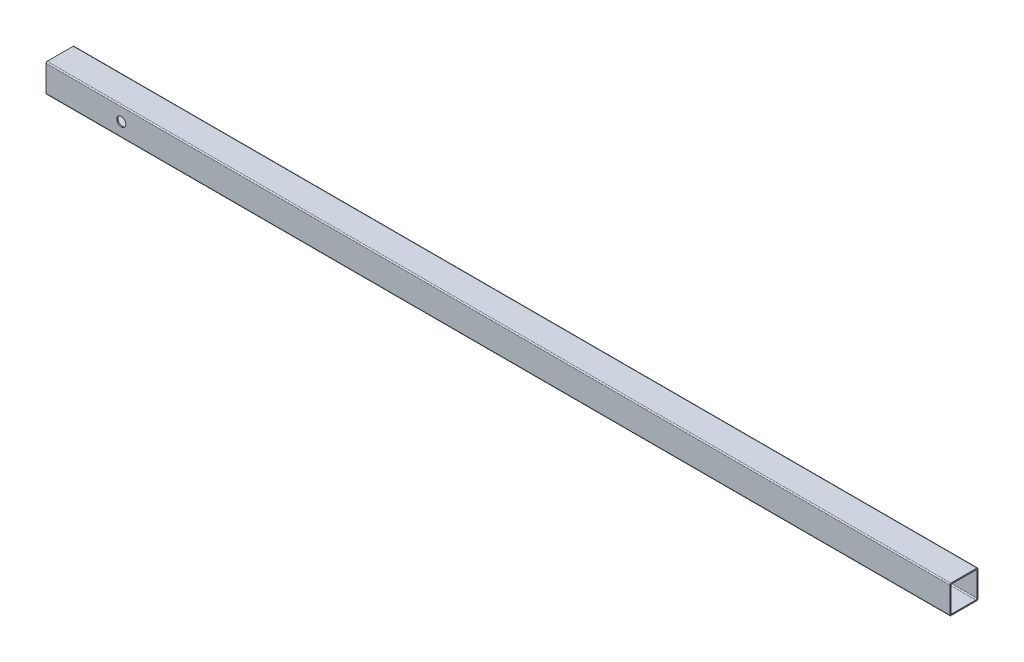
SolidWorks part; units mm, degrees
material "Thornel Mat VMA"
ref_plane "Front Plane" through (0, 0, 0) normal (0, 0, 1) x (1, 0, 0)
ref_plane "Top Plane" through (0, 0, 0) normal (0, 1, 0) x (1, 0, 0)
ref_plane "Right Plane" through (0, 0, 0) normal (1, 0, 0) x (0, 0, -1)
sketch "Sketch2" plane through (0, 0, 0) normal (1, 0, 0) x (0, 0, -1)
  line L1 (0.762, 0) -> (18.288, 0)
  line L2 (0, 0.762) -> (0, 18.288)
  line L3 (0.762, 19.05) -> (18.288, 19.05)
  line L4 (19.05, 0.762) -> (19.05, 18.288)
  line L5 (1.524, 0.762) -> (17.526, 0.762)
  line L6 (0.762, 1.524) -> (0.762, 17.526)
  line L7 (1.524, 18.288) -> (17.526, 18.288)
  line L8 (18.288, 1.524) -> (18.288, 17.526)
  arc A0 (17.526, 18.288) -> (18.288, 17.526) centre (17.526, 17.526) cw
  arc A1 (17.526, 0.762) -> (18.288, 1.524) centre (17.526, 1.524) ccw
  arc A2 (1.524, 0.762) -> (0.762, 1.524) centre (1.524, 1.524) cw
  arc A3 (0.762, 17.526) -> (1.524, 18.288) centre (1.524, 17.526) cw
  arc A4 (18.288, 19.05) -> (19.05, 18.288) centre (18.288, 18.288) cw
  arc A5 (18.288, 0) -> (19.05, 0.762) centre (18.288, 0.762) ccw
  arc A6 (0.762, 0) -> (0, 0.762) centre (0.762, 0.762) cw
  arc A7 (0, 18.288) -> (0.762, 19.05) centre (0.762, 18.288) cw
  point P11 (18.288, 18.288)
  point P14 (18.288, 0.762)
  point P19 (0.762, 18.288)
  point P22 (19.05, 19.05)
  point P25 (19.05, 0)
  point P28 (0, 0)
  point P31 (0, 19.05)
  dimension "D7" = 0.762
  dimension "D1" = 19.05
  dimension "D2" = 19.05
  dimension "D5" = 0.762
  dimension "D6" = 0.762
  dimension "D3" = 0.762
  dimension "D4" = 0.762
extrude "Boss-Extrude1" add sketch "Sketch2" along normal blind 609.6
sketch "Sketch3" plane through (0, 0, 0) normal (0, 0, 1) x (1, 0, 0)
  line L0 (0, 18.288) -> (0, 0.762) construction
  line L1 (609.6, 19.05) -> (0, 19.05) construction
  circle A0 centre (50.8, 9.525) radius 3.048
  dimension "D1" = 6.096
  dimension "D2" = 50.8
  dimension "D3" = 9.525
extrude "Cut-Extrude1" cut sketch "Sketch3" against normal up to surface (19.05 mm away) up to face at (304.8, 9.525, -19.05)
equation "\"shaft\"=0.75"
equation "\"D1@Sketch2\"=\"shaft\""
equation "\"D2@Sketch2\"=\"shaft\""
equation "\"IDshaft\"=0.4375"
equation "\"D3@Sketch3\"=\"shaft\"/2"
